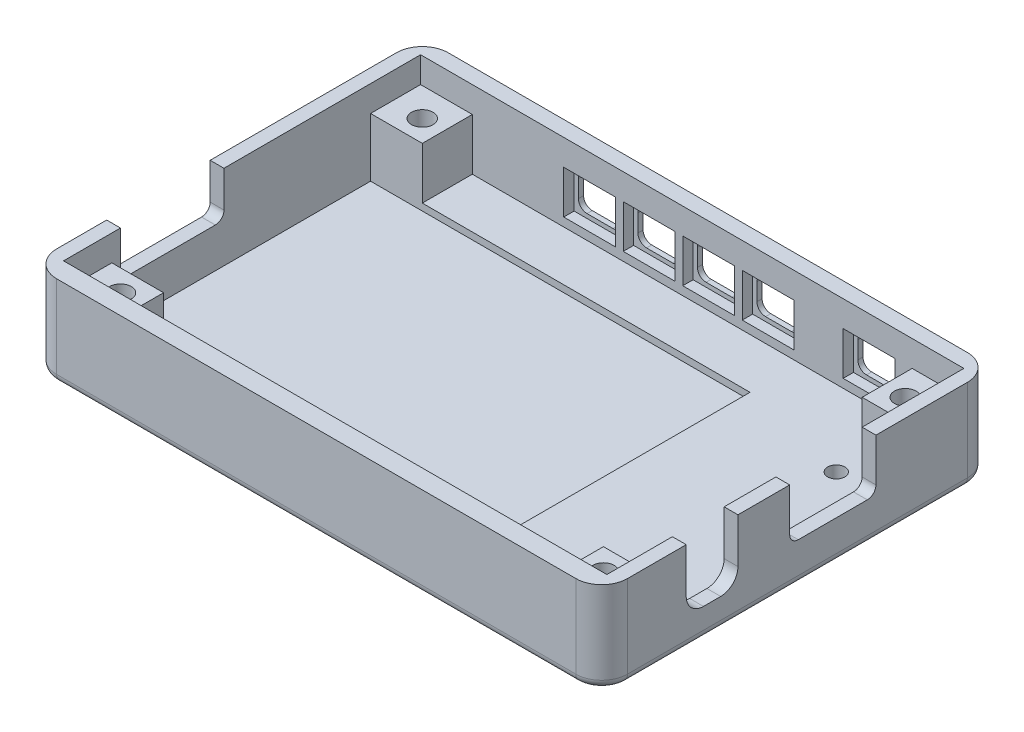
SolidWorks part; units mm, degrees
ref_plane "前视基准面" through (0, 0, 0) normal (0, 0, 1) x (1, 0, 0)
ref_plane "上视基准面" through (0, 0, 0) normal (0, 1, 0) x (1, 0, 0)
ref_plane "右视基准面" through (0, 0, 0) normal (1, 0, 0) x (0, 0, -1)
sketch "草图1" plane through (0, 0, 0) normal (0, 1, 0) x (1, 0, 0)
  line L1 (-31.5, -21) -> (31.5, -21)
  line L2 (-31.5, -21) -> (-31.5, 21)
  line L3 (-31.5, 21) -> (31.5, 21)
  line L4 (31.5, -21) -> (31.5, 21)
  line L5 (-31.5, -21) -> (31.5, 21) construction
  line L6 (-31.5, 21) -> (31.5, -21) construction
  point P0 (0, 0)
  dimension "D1" = 63
  dimension "D2" = 42
extrude "底" add sketch "草图1" against normal blind 1.6
sketch "草图2" plane through (0, 0, 0) normal (0, 1, 0) x (1, 0, 0)
  line L0 (-31.5, 21) -> (-31.5, -21) construction
  line L1 (-31.5, -15) -> (12.5, -15)
  line L2 (-31.5, -15) -> (-31.5, 15)
  line L3 (-31.5, 15) -> (12.5, 15)
  line L4 (12.5, -15) -> (12.5, 15)
  line L5 (-31.5, -15) -> (12.5, 15) construction
  line L6 (-31.5, 15) -> (12.5, -15) construction
  line L7 (31.5, 21) -> (-31.5, 21) construction
  line L8 (-31.5, -21) -> (31.5, -21) construction
  point P0 (-19.9597, 0.5003)
  dimension "D1" = 44
  dimension "D2" = 6
  dimension "D3" = 0
  dimension "D4" = 6
extrude "电池槽" cut sketch "草图2" against normal blind 0.8
sketch "草图4" plane through (0, -1.6, 0) normal (0, -1, 0) x (-1, 0, 0)
  line L0 (-31.5, 21) -> (-31.5, -21)
  line L1 (-31.5, 21) -> (-33.1, 21)
  line L2 (-31.5, -21) -> (-33.1, -21)
  line L3 (-33.1, 21) -> (-33.1, -21)
  line L4 (31.5, 21) -> (31.5, -21)
  line L5 (31.5, 21) -> (33.1, 21)
  line L6 (31.5, -21) -> (33.1, -21)
  line L7 (33.1, 21) -> (33.1, -21)
  dimension "D1" = 1.6
  dimension "D2" = 1.6
extrude "侧边" add sketch "草图4" against normal blind 10.6
sketch "草图5" plane through (0, 0, 0) normal (0, 1, 0) x (1, 0, 0)
  line L0 (-31.5, 21) -> (-31.5, 15)
  line L1 (-31.5, 21) -> (-25.5, 21)
  line L2 (-31.5, 15) -> (-25.5, 15)
  line L3 (-25.5, 21) -> (-25.5, 15)
  line L4 (-31.5, 21) -> (-31.5, 15) construction
  line L5 (25.5, 21) -> (25.5, 15)
  line L6 (25.5, 21) -> (31.5, 21)
  line L7 (25.5, 15) -> (31.5, 15)
  line L8 (31.5, 21) -> (31.5, 15)
  line L9 (-31.5, -15) -> (-31.5, -21)
  line L10 (-31.5, -15) -> (-25.5, -15)
  line L11 (-31.5, -21) -> (-25.5, -21)
  line L12 (-25.5, -15) -> (-25.5, -21)
  line L13 (25.5, -15) -> (25.5, -21)
  line L14 (25.5, -15) -> (31.5, -15)
  line L15 (25.5, -21) -> (31.5, -21)
  line L16 (31.5, -15) -> (31.5, -21)
  dimension "D1" = 6
  dimension "D2" = 6
  dimension "D3" = 6
  dimension "D4" = 6
extrude "螺丝固定" add sketch "草图5" along normal offset from surface (6 mm away) 3 up to face at (-32.3, 9, 0)
sketch "草图6" plane through (0, 9, 0) normal (0, 1, 0) x (1, 0, 0)
  line L0 (-25.5, 15) -> (-25.5, 21) construction
  line L1 (-31.5, 15) -> (-25.5, 15) construction
  circle A0 centre (-28, 17.5) radius 1.25
  circle A1 centre (28, 17.5) radius 1.25
  circle A2 centre (28, -17.5) radius 1.25
  circle A3 centre (-28, -17.5) radius 1.25
  dimension "D1" = 2.5
  dimension "D2" = 2.5
  dimension "D3" = 2.5
  dimension "D4" = 2
  dimension "D5" = 2
extrude "螺丝孔" cut sketch "草图6" against normal up to surface (9 mm away) up to face at (7.3333, 0, 0)
sketch "草图8" plane through (0, 0, 0) normal (0, 1, 0) x (1, 0, 0)
  line L0 (25.5, 21) -> (25.5, 15) construction
  line L1 (-30.5, 20) -> (-25.5, 20)
  line L2 (-30.5, 20) -> (-30.5, 15)
  line L3 (-30.5, 15) -> (-25.5, 15)
  line L4 (-25.5, 20) -> (-25.5, 15)
  line L5 (-30.5, 20) -> (-25.5, 15) construction
  line L6 (-30.5, 15) -> (-25.5, 20) construction
  line L7 (30.5, 20) -> (25.5, 20)
  line L8 (30.5, 20) -> (30.5, 15)
  line L9 (30.5, 15) -> (25.5, 15)
  line L10 (25.5, 20) -> (25.5, 15)
  line L11 (30.5, 20) -> (25.5, 15) construction
  line L12 (30.5, 15) -> (25.5, 20) construction
  line L14 (-30.5, -20) -> (-25.5, -20)
  line L15 (-30.5, -20) -> (-30.5, -15)
  line L16 (-30.5, -15) -> (-25.5, -15)
  line L17 (-25.5, -20) -> (-25.5, -15)
  line L18 (-30.5, -20) -> (-25.5, -15) construction
  line L19 (-30.5, -15) -> (-25.5, -20) construction
  line L20 (30.5, -20) -> (25.5, -20)
  line L21 (30.5, -20) -> (30.5, -15)
  line L22 (30.5, -15) -> (25.5, -15)
  line L23 (25.5, -20) -> (25.5, -15)
  line L24 (30.5, -20) -> (25.5, -15) construction
  line L25 (30.5, -15) -> (25.5, -20) construction
  circle A0 centre (28, 17.5) radius 1.25 construction
  circle A1 centre (28, -17.5) radius 1.25 construction
  circle A2 centre (-28, -17.5) radius 1.25 construction
  circle A3 centre (-28, 17.5) radius 1.25 construction
  circle A4 centre (28, 17.5) radius 1.25 construction
  circle A5 centre (28, -17.5) radius 1.25 construction
  circle A6 centre (-28, -17.5) radius 1.25 construction
  circle A7 centre (-28, 17.5) radius 1.25 construction
  point P0 (0, 0)
sketch "草图9" plane through (0, 0, -21) normal (0, 0, -1) x (-1, 0, 0)
  line L0 (-33.1, 9) -> (-33.1, -1.6)
  line L1 (-33.1, 9) -> (33.1, 9)
  line L2 (-33.1, -1.6) -> (33.1, -1.6)
  line L3 (33.1, 9) -> (33.1, -1.6)
extrude "凸台-拉伸4" add sketch "草图9" along normal blind 1.6
sketch "草图10" plane through (0, 0, -21) normal (0, 0, 1) x (1, 0, 0)
  line L1 (17.5, 1) -> (23.5, 1)
  line L2 (17.5, 1) -> (17.5, 6)
  line L3 (17.5, 6) -> (23.5, 6)
  line L4 (23.5, 1) -> (23.5, 6)
  line L5 (17.5, 1) -> (23.5, 6) construction
  line L6 (17.5, 6) -> (23.5, 1) construction
  line L7 (25.5, 0) -> (-25.5, 0) construction
  line L8 (25.5, 6) -> (25.5, 0) construction
  line L9 (5.8, 1) -> (11.8, 1)
  line L10 (5.8, 1) -> (5.8, 6)
  line L11 (5.8, 6) -> (11.8, 6)
  line L12 (11.8, 1) -> (11.8, 6)
  line L13 (5.8, 1) -> (11.8, 6) construction
  line L14 (5.8, 6) -> (11.8, 1) construction
  line L15 (-1.1, 1) -> (4.9, 1)
  line L16 (-1.1, 1) -> (-1.1, 6)
  line L17 (-1.1, 6) -> (4.9, 6)
  line L18 (4.9, 1) -> (4.9, 6)
  line L19 (-1.1, 1) -> (4.9, 6) construction
  line L20 (-1.1, 6) -> (4.9, 1) construction
  line L21 (-8, 1) -> (-2, 1)
  line L22 (-8, 1) -> (-8, 6)
  line L23 (-8, 6) -> (-2, 6)
  line L24 (-2, 1) -> (-2, 6)
  line L25 (-8, 1) -> (-2, 6) construction
  line L26 (-8, 6) -> (-2, 1) construction
  line L27 (-14.9, 1) -> (-8.9, 1)
  line L28 (-14.9, 1) -> (-14.9, 6)
  line L29 (-14.9, 6) -> (-8.9, 6)
  line L30 (-8.9, 1) -> (-8.9, 6)
  line L31 (-14.9, 1) -> (-8.9, 6) construction
  line L32 (-14.9, 6) -> (-8.9, 1) construction
  point P0 (20.5, 3.5)
  point P11 (8.8, 3.5)
  point P16 (1.9, 3.5)
  point P21 (-5, 3.5)
  point P26 (-11.9, 3.5)
  dimension "D1" = 6
  dimension "D2" = 5
  dimension "D3" = 5
  dimension "D4" = 3.5
  dimension "D5" = 2
  dimension "D6" = 4
extrude "按键底" cut sketch "草图10" against normal blind 1
sketch "草图12" plane through (0, 0, -22) normal (0, 0, 1) x (1, 0, 0)
  line L0 (17.5, 6) -> (23.5, 1) construction
  line L1 (6.3, 2.5) -> (6.3, 4.5)
  line L2 (19, 1.5) -> (22, 1.5)
  line L3 (18, 2.5) -> (18, 4.5)
  line L4 (23.5, 1) -> (23.5, 6)
  line L5 (23.5, 6) -> (17.5, 6)
  line L6 (17.5, 6) -> (17.5, 1)
  line L7 (17.5, 1) -> (23.5, 1)
  line L8 (23.5, 1) -> (23.5, 6) construction
  line L9 (23.5, 6) -> (17.5, 6) construction
  line L10 (17.5, 6) -> (17.5, 1) construction
  line L11 (17.5, 1) -> (23.5, 1) construction
  line L12 (19, 5.5) -> (22, 5.5)
  line L13 (23, 2.5) -> (23, 4.5)
  line L14 (18, 1.5) -> (23, 5.5) construction
  line L15 (18, 5.5) -> (23, 1.5) construction
  line L16 (7.3, 1.5) -> (10.3, 1.5)
  line L17 (7.3, 5.5) -> (10.3, 5.5)
  line L18 (11.3, 2.5) -> (11.3, 4.5)
  line L19 (-0.6, 2.5) -> (-0.6, 4.5)
  line L20 (0.4, 1.5) -> (3.4, 1.5)
  line L21 (0.4, 5.5) -> (3.4, 5.5)
  line L22 (4.4, 2.5) -> (4.4, 4.5)
  line L23 (-7.5, 2.5) -> (-7.5, 4.5)
  line L24 (-6.5, 1.5) -> (-3.5, 1.5)
  line L25 (-6.5, 5.5) -> (-3.5, 5.5)
  line L26 (-2.5, 2.5) -> (-2.5, 4.5)
  line L27 (-14.4, 2.5) -> (-14.4, 4.5)
  line L28 (-13.4, 1.5) -> (-10.4, 1.5)
  line L29 (-13.4, 5.5) -> (-10.4, 5.5)
  line L30 (-9.4, 2.5) -> (-9.4, 4.5)
  arc A0 (22, 5.5) -> (23, 4.5) centre (22, 4.5) cw
  arc A1 (22, 1.5) -> (23, 2.5) centre (22, 2.5) ccw
  arc A2 (19, 1.5) -> (18, 2.5) centre (19, 2.5) cw
  arc A3 (18, 4.5) -> (19, 5.5) centre (19, 4.5) cw
  arc A4 (6.3, 4.5) -> (7.3, 5.5) centre (7.3, 4.5) cw
  arc A5 (7.3, 1.5) -> (6.3, 2.5) centre (7.3, 2.5) cw
  arc A6 (10.3, 5.5) -> (11.3, 4.5) centre (10.3, 4.5) cw
  arc A7 (10.3, 1.5) -> (11.3, 2.5) centre (10.3, 2.5) ccw
  arc A8 (-0.6, 4.5) -> (0.4, 5.5) centre (0.4, 4.5) cw
  arc A9 (0.4, 1.5) -> (-0.6, 2.5) centre (0.4, 2.5) cw
  arc A10 (3.4, 5.5) -> (4.4, 4.5) centre (3.4, 4.5) cw
  arc A11 (3.4, 1.5) -> (4.4, 2.5) centre (3.4, 2.5) ccw
  arc A12 (-7.5, 4.5) -> (-6.5, 5.5) centre (-6.5, 4.5) cw
  arc A13 (-6.5, 1.5) -> (-7.5, 2.5) centre (-6.5, 2.5) cw
  arc A14 (-3.5, 5.5) -> (-2.5, 4.5) centre (-3.5, 4.5) cw
  arc A15 (-3.5, 1.5) -> (-2.5, 2.5) centre (-3.5, 2.5) ccw
  arc A16 (-14.4, 4.5) -> (-13.4, 5.5) centre (-13.4, 4.5) cw
  arc A17 (-13.4, 1.5) -> (-14.4, 2.5) centre (-13.4, 2.5) cw
  arc A18 (-10.4, 5.5) -> (-9.4, 4.5) centre (-10.4, 4.5) cw
  arc A19 (-10.4, 1.5) -> (-9.4, 2.5) centre (-10.4, 2.5) ccw
  point P2 (20.5, 3.5)
  dimension "D4" = 1
  dimension "D2" = 5
  dimension "D3" = 4
  dimension "D1" = 0
  dimension "D5" = 2
  dimension "D6" = 4
extrude "按键头" cut sketch "草图12" against normal up to next
fillet "圆角4" radius 1 3 edges at (-33.1, -1.6, -0.8) (33.1, -1.6, -0.8) (0, -1.6, -22.6)
fillet "圆角5" radius 3 4 edges at (-32.8071, -1.3071, -22.3071) (32.8071, -1.3071, -22.3071) (33.1, 4.2, -22.6) (-33.1, 4.2, -22.6)
sketch "草图15" plane through (0, 9, 0) normal (0, 1, 0) x (1, 0, 0)
  line L8 (-31.5, 21) -> (31.5, 21)
  line L10 (-31.5, 21) -> (31.5, 21)
  line L16 (33.1, -21) -> (33.1, 19.6)
  line L17 (30.1, 22.6) -> (-30.1, 22.6)
  line L18 (-33.1, 19.6) -> (-33.1, -21)
  line L19 (-33.1, -21) -> (-31.5, -21)
  line L22 (-31.5, -21) -> (-31.5, 21)
  line L28 (31.5, 21) -> (31.5, -21)
  line L31 (31.5, -21) -> (33.1, -21)
  line L32 (33.1, -21) -> (33.1, 19.6)
  line L33 (30.1, 22.6) -> (-30.1, 22.6)
  line L34 (-33.1, 19.6) -> (-33.1, -21)
  line L35 (-33.1, -21) -> (-31.5, -21)
  line L38 (-31.5, -21) -> (-31.5, 21)
  line L44 (31.5, 21) -> (31.5, -21)
  line L47 (31.5, -21) -> (33.1, -21)
  arc A2 (33.1, 19.6) -> (30.1, 22.6) centre (30.1, 19.6) ccw
  arc A3 (-30.1, 22.6) -> (-33.1, 19.6) centre (-30.1, 19.6) ccw
  arc A4 (33.1, 19.6) -> (30.1, 22.6) centre (30.1, 19.6) ccw
  arc A5 (-30.1, 22.6) -> (-33.1, 19.6) centre (-30.1, 19.6) ccw
  dimension "D1" = 0
sketch "草图16" plane through (-31.5, 0, 0) normal (1, 0, 0) x (0, 0, -1)
  line L0 (-14, 9) -> (-2, 9)
  line L1 (-14, 9) -> (-14, 4.8)
  line L2 (-2, 9) -> (-2, 4.8)
  line L3 (-13, 3.8) -> (-3, 3.8)
  line L4 (-21, 9) -> (21, 9) construction
  line L5 (-15, 6) -> (-15, -0.8) construction
  arc A0 (-14, 4.8) -> (-13, 3.8) centre (-13, 4.8) ccw
  arc A1 (-2, 4.8) -> (-3, 3.8) centre (-3, 4.8) cw
  point P10 (-14, 3.8)
  point P13 (-2, 3.8)
  dimension "D4" = 1
  dimension "D1" = 12
  dimension "D2" = 5.2
  dimension "D3" = 1
extrude "tf口" cut sketch "草图16" against normal up to next
sketch "草图17" plane through (31.5, 0, 0) normal (-1, 0, 0) x (0, 0, 1)
  line L0 (7, 9) -> (13, 9)
  line L1 (7, 9) -> (7, 3.8)
  line L2 (13, 9) -> (13, 3.8)
  line L3 (9, 1.8) -> (11, 1.8)
  line L4 (-21, 9) -> (21, 9) construction
  line L5 (15, -0.8) -> (15, 6) construction
  line L6 (1, 9) -> (-9, 9)
  line L7 (1, 9) -> (1, 4)
  line L8 (-9, 9) -> (-9, 4)
  line L9 (0, 3) -> (-8, 3)
  line L11 (21, 9) -> (-21, 9) construction
  arc A0 (13, 3.8) -> (11, 1.8) centre (11, 3.8) cw
  arc A1 (7, 3.8) -> (9, 1.8) centre (9, 3.8) ccw
  arc A2 (1, 4) -> (0, 3) centre (0, 4) cw
  arc A3 (-9, 4) -> (-8, 3) centre (-8, 4) ccw
  point P10 (13, 1.8)
  point P13 (7, 1.8)
  point P22 (1, 3)
  point P25 (-9, 3)
  dimension "D4" = 2
  dimension "D8" = 1
  dimension "D1" = 6
  dimension "D2" = 7.2
  dimension "D3" = 2
  dimension "D5" = 10
  dimension "D6" = 14
  dimension "D7" = 6
extrude "耳机和usb口" cut sketch "草图17" against normal up to next
sketch "草图18" plane through (0, 0, 21) normal (0, 0, 1) x (1, 0, 0)
  line L0 (33.1, 9) -> (33.1, -0.6) construction
  line L1 (-32.1, -1.6) -> (32.1, -1.6) construction
  line L2 (-33.1, 9) -> (-33.1, -0.6) construction
  line L3 (33.1, 9) -> (33.1, -0.6)
  line L4 (-32.1, -1.6) -> (32.1, -1.6)
  line L5 (-33.1, 9) -> (-33.1, -0.6)
  line L6 (-33.1, 9) -> (33.1, 9)
  arc A0 (32.1, -1.6) -> (33.1, -0.6) centre (32.1, -0.6) ccw construction
  arc A1 (-33.1, -0.6) -> (-32.1, -1.6) centre (-32.1, -0.6) ccw construction
  arc A2 (32.1, -1.6) -> (33.1, -0.6) centre (32.1, -0.6) ccw
  arc A3 (-33.1, -0.6) -> (-32.1, -1.6) centre (-32.1, -0.6) ccw
extrude "封底" add sketch "草图18" along normal blind 1.8
fillet "圆角7" radius 3 2 edges at (33.1, 4.2, 22.8) (-33.1, 4.2, 22.8) tangent propagation no
fillet "圆角8" radius 1 3 edges at (-31.1705, -1.6, 22.6025) (31.1705, -1.6, 22.6025) (0, -1.6, 22.8)
sketch "草图19" plane through (0, 0, 21) normal (0, 0, -1) x (-1, 0, 0)
  line L8 (31.5, 9) -> (-31.5, 9)
  line L9 (-31.5, 9) -> (-31.5, 6)
  line L10 (-31.5, 6) -> (-25.5, 6)
  line L11 (-25.5, 6) -> (-25.5, 0)
  line L12 (-25.5, 0) -> (25.5, 0)
  line L13 (25.5, 0) -> (25.5, 6)
  line L14 (25.5, 6) -> (31.5, 6)
  line L15 (31.5, 6) -> (31.5, 9)
  line L16 (31.5, 9) -> (-31.5, 9)
  line L17 (-31.5, 9) -> (-31.5, 6)
  line L18 (-31.5, 6) -> (-25.5, 6)
  line L19 (-25.5, 6) -> (-25.5, 0)
  line L20 (-25.5, 0) -> (25.5, 0)
  line L21 (25.5, 0) -> (25.5, 6)
  line L22 (25.5, 6) -> (31.5, 6)
  line L23 (31.5, 6) -> (31.5, 9)
  dimension "D1" = 0
extrude "凸台-拉伸5" add sketch "草图19" along normal blind 0.4
sketch "草图24" plane through (0, 0, 0) normal (0, 1, 0) x (1, 0, 0)
  line L12 (-25.5, -15) -> (-25.5, -20.6)
  line L13 (-25.5, -20.6) -> (25.5, -20.6)
  line L14 (25.5, -20.6) -> (25.5, -15)
  line L15 (25.5, -15) -> (31.5, -15)
  line L16 (31.5, -15) -> (31.5, 15)
  line L17 (31.5, 15) -> (25.5, 15)
  line L18 (25.5, 15) -> (25.5, 21)
  line L19 (25.5, 21) -> (-25.5, 21)
  line L20 (-25.5, 21) -> (-25.5, 15)
  line L21 (-25.5, 15) -> (12.5, 15)
  line L22 (12.5, 15) -> (12.5, -15)
  line L23 (12.5, -15) -> (-25.5, -15)
  line L24 (-25.5, -15) -> (-25.5, -20.6)
  line L25 (-25.5, -20.6) -> (25.5, -20.6)
  line L26 (25.5, -20.6) -> (25.5, -15)
  line L27 (25.5, -15) -> (31.5, -15)
  line L28 (31.5, -15) -> (31.5, 15)
  line L29 (31.5, 15) -> (25.5, 15)
  line L30 (25.5, 15) -> (25.5, 21)
  line L32 (-25.5, 21) -> (-25.5, 15)
  line L33 (-25.5, 15) -> (12.5, 15)
  line L34 (12.5, 15) -> (12.5, -15)
  line L35 (12.5, -15) -> (-25.5, -15)
  line L37 (25.5, 21) -> (-25.5, 21)
  dimension "D1" = 0
sketch "草图25" plane through (0, 0, 0) normal (0, 1, 0) x (1, 0, 0)
  circle A0 centre (25.5, 12) radius 1
  point P0 (28, 17.5)
  point P3 (28, 17.5)
  dimension "D1" = 2
  dimension "D2" = 2.5
  dimension "D3" = 5.5
extrude "BOOT孔" cut sketch "草图25" against normal up to next
sketch "草图27" plane through (0, 0, -21) normal (0, 0, 1) x (1, 0, 0)
  line L4 (5.8, 1) -> (11.8, 1)
  line L5 (11.8, 1) -> (11.8, 6)
  line L6 (11.8, 6) -> (5.8, 6)
  line L7 (5.8, 6) -> (5.8, 1)
  line L8 (31.5, 6) -> (31.5, 9)
  line L9 (31.5, 9) -> (-31.5, 9)
  line L10 (-31.5, 9) -> (-31.5, 6)
  line L11 (-31.5, 6) -> (-25.5, 6)
  line L12 (-25.5, 6) -> (-25.5, 0)
  line L13 (-25.5, 0) -> (25.5, 0)
  line L14 (25.5, 0) -> (25.5, 6)
  line L15 (25.5, 6) -> (31.5, 6)
  line L16 (31.5, 6) -> (31.5, 9)
  line L17 (31.5, 9) -> (-31.5, 9)
  line L18 (-31.5, 9) -> (-31.5, 6)
  line L19 (-31.5, 6) -> (-25.5, 6)
  line L20 (-25.5, 6) -> (-25.5, 0)
  line L21 (-25.5, 0) -> (25.5, 0)
  line L22 (25.5, 0) -> (25.5, 6)
  line L23 (25.5, 6) -> (31.5, 6)
  line L24 (5.8, 1) -> (11.8, 1)
  line L25 (11.8, 1) -> (11.8, 6)
  line L26 (11.8, 6) -> (5.8, 6)
  line L27 (5.8, 6) -> (5.8, 1)
  line L28 (17.5, 1) -> (23.5, 1)
  line L29 (23.5, 1) -> (23.5, 6)
  line L30 (23.5, 6) -> (17.5, 6)
  line L31 (17.5, 6) -> (17.5, 1)
  line L32 (17.5, 1) -> (23.5, 1)
  line L33 (23.5, 1) -> (23.5, 6)
  line L34 (23.5, 6) -> (17.5, 6)
  line L35 (17.5, 6) -> (17.5, 1)
  line L36 (-14.9, 1) -> (-8.9, 1)
  line L37 (-8.9, 1) -> (-8.9, 6)
  line L38 (-8.9, 6) -> (-14.9, 6)
  line L39 (-14.9, 6) -> (-14.9, 1)
  line L40 (-14.9, 1) -> (-8.9, 1)
  line L41 (-8.9, 1) -> (-8.9, 6)
  line L42 (-8.9, 6) -> (-14.9, 6)
  line L43 (-14.9, 6) -> (-14.9, 1)
  line L44 (-8, 1) -> (-2, 1)
  line L45 (-2, 1) -> (-2, 6)
  line L46 (-2, 6) -> (-8, 6)
  line L47 (-8, 6) -> (-8, 1)
  line L48 (-8, 1) -> (-2, 1)
  line L49 (-2, 1) -> (-2, 6)
  line L50 (-2, 6) -> (-8, 6)
  line L51 (-8, 6) -> (-8, 1)
  line L52 (-1.1, 1) -> (4.9, 1)
  line L53 (4.9, 1) -> (4.9, 6)
  line L54 (4.9, 6) -> (-1.1, 6)
  line L55 (-1.1, 6) -> (-1.1, 1)
  line L56 (-1.1, 1) -> (4.9, 1)
  line L57 (4.9, 1) -> (4.9, 6)
  line L58 (4.9, 6) -> (-1.1, 6)
  line L59 (-1.1, 6) -> (-1.1, 1)
  dimension "D1" = 0
  dimension "D2" = 0
  dimension "D3" = 0
  dimension "D4" = 0
  dimension "D5" = 0
  dimension "D6" = 0
extrude "凸台-拉伸8" add sketch "草图27" along normal blind 0.2
